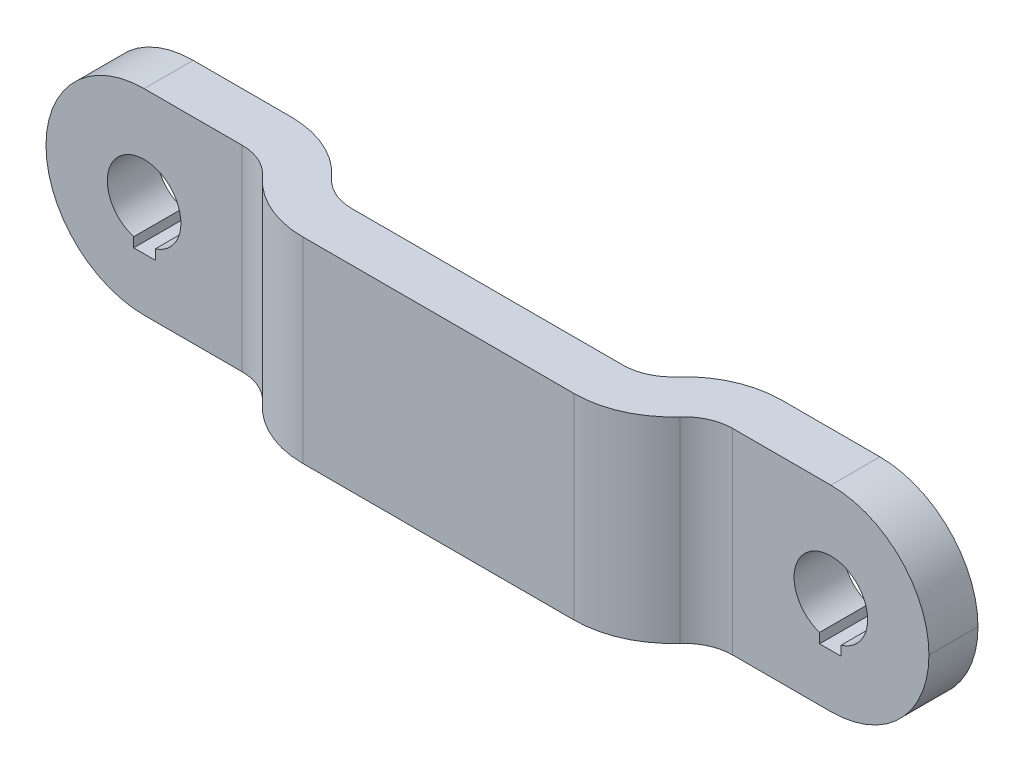
SolidWorks part; units mm, degrees
material "1023 Carbon Steel Sheet (SS)"
ref_plane "front" through (0, 0, 0) normal (0, 0, 1) x (1, 0, 0)
ref_plane "top" through (0, 0, 0) normal (0, 1, 0) x (1, 0, 0)
ref_plane "side" through (0, 0, 0) normal (1, 0, 0) x (0, 0, -1)
sketch "Sketch1" plane through (0, 0, 0) normal (0, 1, 0) x (1, 0, 0)
  line L0 (-28.575, 0) -> (-15.875, 0)
  line L1 (-28.575, 0) -> (-28.575, -3.175)
  line L2 (-28.575, -3.175) -> (-15.875, -3.175)
  line L3 (-8.7755, -6.35) -> (8.7755, -6.35)
  line L4 (0, 0) -> (0, 21.9313) construction
  line L5 (-8.7755, -3.175) -> (8.7755, -3.175)
  line L6 (28.575, -3.175) -> (15.875, -3.175)
  line L7 (28.575, 0) -> (28.575, -3.175)
  line L8 (28.575, 0) -> (15.875, 0)
  line L9 (-50, 0) -> (50, 0) construction
  arc A0 (-15.875, -3.175) -> (-13.5085, -4.2333) centre (-15.875, -6.35) cw
  arc A1 (-13.5085, -4.2333) -> (-8.7755, -6.35) centre (-8.7755, 0) ccw
  arc A2 (-15.875, 0) -> (-11.142, -2.1167) centre (-15.875, -6.35) cw
  arc A3 (-11.142, -2.1167) -> (-8.7755, -3.175) centre (-8.7755, 0) ccw
  arc A4 (11.142, -2.1167) -> (8.7755, -3.175) centre (8.7755, 0) cw
  arc A5 (15.875, 0) -> (11.142, -2.1167) centre (15.875, -6.35) ccw
  arc A6 (13.5085, -4.2333) -> (8.7755, -6.35) centre (8.7755, 0) cw
  arc A7 (15.875, -3.175) -> (13.5085, -4.2333) centre (15.875, -6.35) ccw
  dimension "D5" = 6.35
  dimension "D3" = 6.35
  dimension "D1" = 3.175
  dimension "D2" = 57.15
  dimension "D4" = 31.75
  dimension "D7" = 3.175
extrude "Base-Extrude" add sketch "Sketch1" along normal mid plane 12.7
fillet "Fillet1" radius 6.35
sketch "Sketch2" plane through (0, 0, 3.175) normal (0, 0, 1) x (1, 0, 0)
  line L0 (0, 0) -> (0, 14.5198) construction
  line L1 (-22.8956, -2.2849) -> (-22.8956, -2.9089)
  line L2 (-21.4987, -2.9089) -> (-22.8956, -2.9089)
  line L3 (21.4987, -2.2678) -> (21.4987, -2.9089)
  line L4 (21.4987, -2.9089) -> (22.8956, -2.9089)
  line L5 (22.8956, -2.2849) -> (22.8956, -2.9089)
  line L6 (-21.4987, -2.2678) -> (-21.4987, -2.9089)
  arc A0 (22.8956, -2.2849) -> (21.4987, -2.2678) centre (22.225, 0) ccw
  arc A1 (-22.8956, -2.2849) -> (-21.4987, -2.2678) centre (-22.225, 0) cw
  arc A2 (28.575, 0) -> (22.225, 6.35) centre (22.225, 0) ccw construction
  dimension "D1" = 4.7625
extrude "Cut-Extrude1" cut sketch "Sketch2" against normal through all
